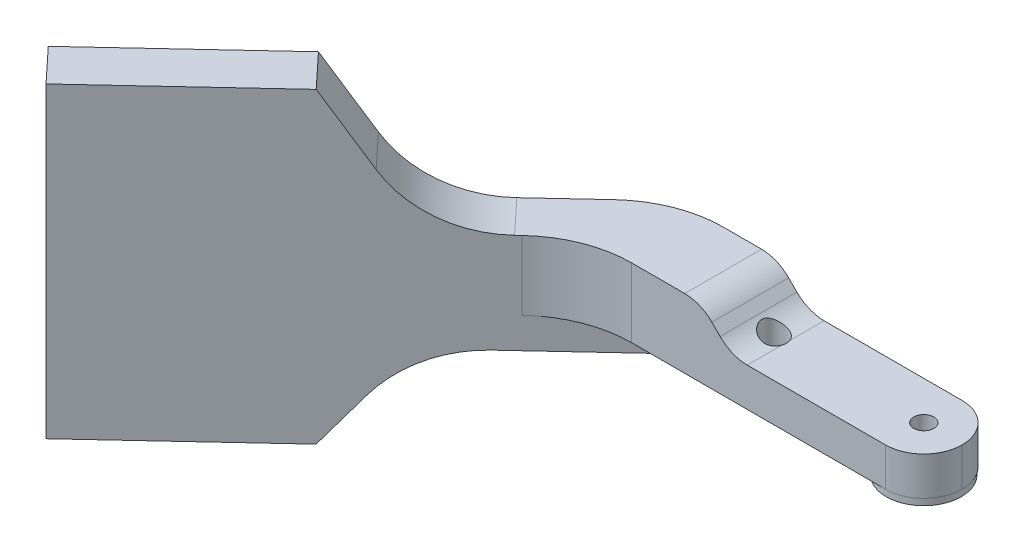
SolidWorks part; units mm, degrees
ref_plane "Front" through (0, 0, 0) normal (0, 0, 1) x (1, 0, 0)
ref_plane "Top" through (0, 0, 0) normal (0, 1, 0) x (1, 0, 0)
ref_plane "Right" through (0, 0, 0) normal (1, 0, 0) x (0, 0, -1)
sketch "Sketch1" plane through (0, 0, 0) normal (0, 1, 0) x (1, 0, 0)
  line L0 (0, 10) -> (0, 0)
  line L1 (0, 0) -> (42, 0)
  line L3 (0, 10) -> (42, 10)
  line L4 (42, 0) -> (42, 10)
  line L9 (0, 10) -> (-42.4185, -29.5559)
  line L10 (-42.4185, -29.5559) -> (-38.3265, -33.944)
  line L11 (0, 10) -> (4.092, 5.6119)
  line L12 (-38.3265, -33.944) -> (4.092, 5.6119)
  line L13 (0, 0) -> (-1.926, 0)
  line L14 (-1.926, 0) -> (0, 1.796)
  line L15 (0, 1.796) -> (0, 0)
  dimension "D1" = 10
  dimension "D2" = 42
  dimension "D3" = 223
  dimension "D4" = 58
  dimension "D5" = 6
  dimension "D6" = 270
extrude "Boss-Extrude1" add sketch "Sketch1" along normal blind 5 contours L10 L12 L1 L0 L9 | L1 L12 L11 L0 | L12 L1 L4 L3 L11 | L13 L0 L12 region at (1.364, 0, -5.8026) region at (-20.2035, 0, 12.8728) region at (21.8174, 0, -4.9666) region at (-0.642, 0, -0.5987)
fillet "Fillet1" radius 5 2 edges at (42, 2.5, 0) (42, 2.5, -10)
sketch "Sketch2" plane through (0, 5, 0) normal (0, 1, 0) x (1, 0, 0)
  circle A0 centre (37, 5) radius 1.3
extrude "Cut-Extrude1" cut sketch "Sketch2" against normal blind 10
sketch "Sketch3" plane through (0, 5, 0) normal (0, 1, 0) x (1, 0, 0)
  line L0 (-42.4185, -29.5559) -> (-38.3265, -33.944)
  line L1 (-38.3265, -33.944) -> (-20.1263, -16.972)
  line L2 (-38.3265, -33.944) -> (-1.926, 0) construction
  line L3 (-20.1263, -16.972) -> (-24.2183, -12.5839)
  line L4 (0, 10) -> (-42.4185, -29.5559) construction
  line L5 (-24.2183, -12.5839) -> (-42.4185, -29.5559)
extrude "Boss-Extrude2" add sketch "Sketch3" along normal blind 20
sketch "Sketch4" plane through (0, 0, 0) normal (0, -1, 0) x (1, 0, 0)
  line L0 (-42.4185, 29.5559) -> (-38.3265, 33.944)
  line L1 (-38.3265, 33.944) -> (-20.1263, 16.972)
  line L2 (-38.3265, 33.944) -> (-1.926, 0) construction
  line L3 (-20.1263, 16.972) -> (-24.2183, 12.5839)
  line L4 (0, -10) -> (-42.4185, 29.5559) construction
  line L5 (-24.2183, 12.5839) -> (-42.4185, 29.5559)
extrude "Boss-Extrude3" add sketch "Sketch4" along normal blind 15
sketch "Sketch5" plane through (-4.9878, 0, -5.3488) normal (-0.682, 0, -0.7314) x (-0.7314, 0, 0.682)
  line L0 (26.2943, -15) -> (26.2943, 0)
  line L1 (26.2943, 0) -> (13.889, 0)
  line L2 (-6.82, 0) -> (26.2943, 0) construction
  line L3 (13.889, 0) -> (26.2943, -15)
  line L4 (13.889, 5) -> (26.2943, 25)
  line L5 (-6.82, 5) -> (26.2943, 5) construction
  line L6 (26.2943, 25) -> (26.2943, 5)
  line L7 (26.2943, 5) -> (13.889, 5)
extrude "Boss-Extrude4" add sketch "Sketch5" against normal blind 6
sketch "Sketch6" plane through (0, 0, 0) normal (0, -1, 0) x (1, 0, 0)
  circle A0 centre (37, -5) radius 4.9
  circle A1 centre (37, -5) radius 1.3
extrude "Boss-Extrude5" add sketch "Sketch6" along normal blind 0.9
sketch "Sketch8" plane through (0, 0, 0) normal (0, -1, 0) x (1, 0, 0)
  line L0 (0, -10) -> (-19.6819, 8.3537)
  line L1 (-24.2183, 12.5839) -> (-15.1456, 4.1235) construction
  line L6 (-19.6819, 8.3537) -> (-15.5899, 12.7418)
  line L7 (-20.1263, 16.972) -> (-11.0536, 8.5116) construction
  line L8 (-15.5899, 12.7418) -> (8.7977, -10)
  line L9 (0, -10) -> (37, -10) construction
  line L10 (8.7977, -10) -> (0, -10)
extrude "Boss-Extrude6" add sketch "Sketch8" along normal blind 4
sketch "Sketch9" plane through (0, 5, 0) normal (0, 1, 0) x (1, 0, 0)
  line L3 (-17.565, -6.3796) -> (-24.2183, -12.5839) construction
  line L4 (-20.8916, -9.4817) -> (0, 10)
  line L6 (-20.8916, -9.4817) -> (-16.7996, -13.8699)
  line L7 (-20.1263, -16.972) -> (-11.0536, -8.5116) construction
  line L9 (-16.7996, -13.8699) -> (8.7977, 10)
  line L10 (0, 10) -> (37, 10) construction
  line L11 (8.7977, 10) -> (0, 10)
  line L12 (37, 0) -> (-1.926, 0) construction
  line L13 (8.7977, 0) -> (-1.926, 0)
  line L14 (-1.926, 0) -> (8.7977, 10)
  line L15 (8.7977, 10) -> (17.9505, 10)
  line L16 (17.9505, 10) -> (17.9505, 0)
  line L17 (17.9505, 0) -> (8.7977, 0)
  line M1 (-15.1456, -4.1235) -> (-11.0536, -8.5116)
  line M2 (-11.0536, -8.5116) -> (-1.926, 0)
  line M3 (-1.926, 0) -> (37, 0)
  line M6 (37, 10) -> (0, 10)
  line M7 (0, 10) -> (-15.1456, -4.1235)
extrude "Boss-Extrude7" add sketch "Sketch9" along normal blind 4 contours L9 M3 | L9 M2 M6 M7 M1 | L6 L9 L4 M1 region at (-15.9726, 5, 8.9967) region at (-4.2059, 5, -1.7921) region at (10.3631, 5, -4.3843)
fillet "Fillet2" radius 15 4 edges at (-15.519, -4, 8.5736) (-14.9141, 9, 8.0096) (-1.926, 4.5, 0) (0, 2.5, -10)
fillet "Fillet7" radius 5 1 edges at (17.9505, 9, -5) profile chamfer
fillet "Fillet8" radius 5 2 edges at (12.9505, 9, -5) (16.9505, 5, -5)
sketch "Sketch10" plane through (0, 0, 0) normal (0, -1, 0) x (-1, 0, 0)
  circle A0 centre (-17.5, 5) radius 1.6
extrude "Cut-Extrude2" cut sketch "Sketch10" against normal blind 10
